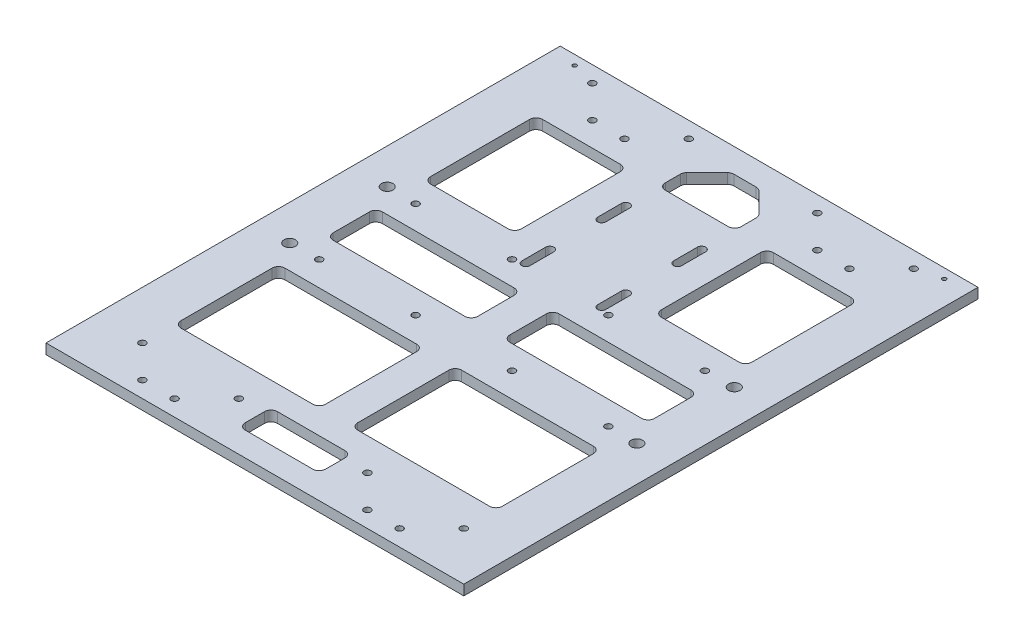
SolidWorks part; units mm, degrees
material "1060 Alloy"
ref_plane "Front Plane" through (0, 0, 0) normal (0, 0, 1) x (1, 0, 0)
ref_plane "Top Plane" through (0, 0, 0) normal (0, 1, 0) x (1, 0, 0)
ref_plane "Right Plane" through (0, 0, 0) normal (1, 0, 0) x (0, 0, -1)
sketch "Sketch1" plane through (0, 0, 0) normal (0, 1, 0) x (1, 0, 0)
  line L1 (-120, 160) -> (120, 160)
  line L2 (-120, 160) -> (-120, -160)
  line L3 (-120, -160) -> (120, -160)
  line L4 (120, 160) -> (120, -160)
  line L5 (-120, 160) -> (120, -160) construction
  line L6 (-120, -160) -> (120, 160) construction
  point P0 (0, 0)
  dimension "D1" = 240
  dimension "D2" = 320
extrude "Boss-Extrude1" add sketch "Sketch1" along normal blind 6.35
hole_wizard "Ø7.1 (7.1) Diameter Hole1" positions "Sketch3" profile "Sketch2" hole size "Ø7.1" standard "ANSI Metric" end condition through all
sketch "Sketch3" plane through (0, 6.35, 0) normal (0, 1, 0) x (1, 0, 0)
  point P0 (-108, 30.32)
  point P2 (108, 30.32)
  point P4 (108, -30.32)
  point P6 (-108, -30.32)
  dimension "D1" = 30.32
  dimension "D2" = 60.64
  dimension "D3" = 108
  dimension "D4" = 108
sketch "Sketch2" plane through (-108, 6.35, -30.32) normal (1, 0, 0) x (0, 0, 1)
  line L0 (0, 0) -> (0, 6.35)
  line L1 (0, 6.35) -> (3.55, 6.35)
  line L2 (3.55, 6.35) -> (3.55, 0)
  line L5 (3.55, 0) -> (0, 0)
  line L11 (0, -6.35) -> (0, 107.95) construction
  dimension "Thru Hole Dia." = 7.1
  dimension "Thru Hole Depth" = 6.35
hole_wizard "M5x0.8 Tapped Hole1" positions "Sketch5" profile "Sketch4" tap size "M5x0.8" standard "ANSI Metric" end condition through all
sketch "Sketch5" plane through (0, 6.35, 0) normal (0, 1, 0) x (1, 0, 0)
  point P0 (-90, 30)
  point P4 (-30, 30)
  point P6 (30, 30)
  point P10 (90, 30)
  point P12 (-90, -30)
  point P16 (-30, -30)
  point P18 (30, -30)
  point P22 (90, -30)
  dimension "D1" = 60
  dimension "D2" = 60
  dimension "D3" = 60
  dimension "D4" = 60
  dimension "D5" = 30
  dimension "D6" = 30
sketch "Sketch4" plane through (-90, 6.35, -30) normal (1, 0, 0) x (0, 0, 1)
  line L0 (0, 0) -> (0, 6.35)
  line L1 (0, 6.35) -> (2.1, 6.35)
  line L2 (2.1, 6.35) -> (2.1, 0)
  line L5 (2.1, 0) -> (0, 0)
  line L11 (0, -6.35) -> (0, 107.95) construction
  dimension "Thru Tap Drill Dia." = 4.2
  dimension "Thru Tap Drill Depth" = 6.35
cosmetic thread "Hole Thread1" parameters "D2"=5
cosmetic thread "Hole Thread2" parameters "D2"=5
cosmetic thread "Hole Thread3" parameters "D2"=5
cosmetic thread "Hole Thread4" parameters "D2"=5
cosmetic thread "Hole Thread5" parameters "D2"=5
cosmetic thread "Hole Thread6" parameters "D2"=5
cosmetic thread "Hole Thread7" parameters "D2"=5
cosmetic thread "Hole Thread8" parameters "D2"=5
hole_wizard "M5x0.8 Tapped Hole3" positions "Sketch9" profile "Sketch8" tap size "M5x0.8" standard "ANSI Metric" end condition through all
sketch "Sketch9" plane through (0, 6.35, 0) normal (0, 1, 0) x (1, 0, 0)
  line L1 (-120, -160) -> (120, -160) construction
  line L2 (120, 160) -> (-120, 160) construction
  point P0 (-80, -150)
  point P2 (-60, -150)
  point P4 (-40, -130)
  point P6 (-100, -130)
  point P16 (-100, 150)
  point P18 (-80, 130)
  point P20 (-60, 130)
  point P22 (-40, 150)
  point P27 (40, 150)
  point P29 (60, 130)
  point P31 (80, 130)
  point P33 (100, 150)
  point P34 (40, -130)
  point P36 (100, -130)
  point P38 (60, -150)
  point P40 (80, -150)
  dimension "D1" = 20
  dimension "D2" = 10
  dimension "D3" = 30
  dimension "D4" = 20
  dimension "D5" = 20
  dimension "D6" = 40
  dimension "D7" = 20
  dimension "D8" = 20
  dimension "D9" = 20
  dimension "D10" = 20
  dimension "D11" = 20
  dimension "D12" = 30
  dimension "D13" = 40
  dimension "D14" = 40
  dimension "D15" = 60
  dimension "D16" = 20
  dimension "D17" = 20
  dimension "D18" = 20
  dimension "D19" = 20
  dimension "D20" = 30
  dimension "D21" = 20
  dimension "D22" = 40
  dimension "D23" = 20
  dimension "D24" = 20
  dimension "D25" = 20
  dimension "D26" = 20
  dimension "D27" = 10
  dimension "D28" = 30
sketch "Sketch8" plane through (-80, 6.35, 150) normal (1, 0, 0) x (0, 0, 1)
  line L0 (0, 0) -> (0, 6.35)
  line L1 (0, 6.35) -> (2.1, 6.35)
  line L2 (2.1, 6.35) -> (2.1, 0)
  line L5 (2.1, 0) -> (0, 0)
  line L11 (0, -6.35) -> (0, 107.95) construction
  dimension "Thru Tap Drill Dia." = 4.2
  dimension "Thru Tap Drill Depth" = 6.35
cosmetic thread "Hole Thread15" parameters "D2"=5
cosmetic thread "Hole Thread16" parameters "D2"=5
cosmetic thread "Hole Thread17" parameters "D2"=5
cosmetic thread "Hole Thread18" parameters "D2"=5
cosmetic thread "Hole Thread19" parameters "D2"=5
cosmetic thread "Hole Thread20" parameters "D2"=5
cosmetic thread "Hole Thread21" parameters "D2"=5
cosmetic thread "Hole Thread22" parameters "D2"=5
cosmetic thread "Hole Thread23" parameters "D2"=5
cosmetic thread "Hole Thread24" parameters "D2"=5
cosmetic thread "Hole Thread25" parameters "D2"=5
cosmetic thread "Hole Thread26" parameters "D2"=5
cosmetic thread "Hole Thread27" parameters "D2"=5
cosmetic thread "Hole Thread28" parameters "D2"=5
cosmetic thread "Hole Thread29" parameters "D2"=5
cosmetic thread "Hole Thread30" parameters "D2"=5
hole_wizard "Ø5.0mm Clearance Dowel Slot1" positions "Sketch11" profile "Sketch10" size "Ø5.0" standard "ANSI Metric" slot yes end condition through all
sketch "Sketch11" plane through (0, 6.35, 0) normal (0, 1, 0) x (1, 0, 0)
  line L5 (-23.6, 76.88) -> (-23.6, 96.88) construction
  line L7 (-23.6, 86.88) -> (23.6, 86.88) construction
  line L10 (0, 86.88) -> (0, 63.28) construction
  circle A0 centre (108, 30.32) radius 3.55 construction
  point P0 (-23.6, 86.88)
  point P2 (23.6, 86.88)
  point P4 (-23.6, 39.68)
  point P6 (23.6, 39.68)
  dimension "D1" = 47.2
  dimension "D2" = 47.2
  dimension "D3" = 47.2
  dimension "D4" = 47.2
  dimension "D5" = 9.36
  dimension "D6" = 23.6
  dimension "D7" = 20
sketch "Sketch10" plane through (-23.6, 6.35, -86.88) normal (1, 0, 0) x (0, 0, 1)
  line L0 (0, 0) -> (0, 6.35)
  line L1 (0, 6.35) -> (2.55, 6.35)
  line L2 (2.55, 6.35) -> (2.55, 0)
  line L5 (2.55, 0) -> (0, 0)
  line L11 (0, -6.35) -> (0, 107.95) construction
  dimension "Thru Hole Dia." = 5.1
  dimension "Thru Hole Depth" = 6.35
sketch "Sketch12" plane through (0, 6.35, 0) normal (0, 1, 0) x (1, 0, 0)
  line L0 (-120, 160) -> (-120, -160) construction
  line L1 (-23.6, 130) -> (-8.6, 145)
  line L2 (-100, 115) -> (-43.6, 115)
  line L3 (-100, 115) -> (-100, 45.32)
  line L4 (-100, 45.32) -> (-43.6, 45.32)
  line L5 (-43.6, 115) -> (-43.6, 45.32)
  line L6 (-8.6, 145) -> (0, 145)
  line L7 (0, 145) -> (0, 130)
  line L8 (0, 130) -> (-23.6, 130)
  line L9 (120, 160) -> (-120, 160) construction
  line L10 (-100, 15.32) -> (-10, 15.32)
  line L11 (-100, 15.32) -> (-100, -15.32)
  line L12 (-100, -15.32) -> (-10, -15.32)
  line L14 (-10, 15.32) -> (-10, -15.32)
  line L15 (0, -125) -> (-25, -125)
  line L16 (0, -125) -> (0, -145)
  line L17 (0, -145) -> (-25, -145)
  line L18 (-25, -125) -> (-25, -145)
  line L19 (-100, -45.32) -> (-10, -45.32)
  line L20 (-100, -45.32) -> (-100, -110)
  line L21 (-100, -110) -> (-10, -110)
  line L22 (-10, -45.32) -> (-10, -110)
  line L23 (-23.6, 130) -> (-23.6, 115)
  line L24 (-23.6, 115) -> (0, 115)
  line L25 (0, 115) -> (0, 130)
  line L26 (-120, -160) -> (120, -160) construction
  circle A10 centre (-108, 30.32) radius 3.55 construction
  circle A11 centre (-108, -30.32) radius 3.55 construction
  circle A12 centre (-80, 130) radius 2.1 construction
  arc A13 (-21.05, 47.13) -> (-26.15, 47.13) centre (-23.6, 47.13) ccw construction
  circle A14 centre (-100, -130) radius 2.1 construction
  circle A15 centre (-40, -130) radius 2.1 construction
  point P27 (0, 160)
  point P32 (-23.6, 49.68)
  dimension "D3" = 15
  dimension "D7" = 15
  dimension "D10" = 20
  dimension "D15" = 20
  dimension "D8" = 15
  dimension "D1" = 10
  dimension "D2" = 20
  dimension "D4" = 15
  dimension "D5" = 15
  dimension "D6" = 15
  dimension "D9" = 20
  dimension "D11" = 45
  dimension "D12" = 20
  dimension "D13" = 15
  dimension "D14" = 10
  dimension "D16" = 15
  dimension "D17" = 20
  dimension "D18" = 15
  dimension "D19" = 15
  dimension "D20" = 15
extrude "Cut-Extrude1" cut sketch "Sketch12" against normal blind 10 contours L15 L18 L17 L16 | L22 L19 L20 L21 | L5 L2 L3 L4 | L24 L25 L8 L23 | L8 L7 L6 L1 | L12 L14 L10 L11 region at (-8.6323, 6.35, -136.3354) region at (-11.8, 6.35, -122.5) region at (-71.8, 6.35, -80.16) region at (-12.5, 6.35, 135) region at (-55, 6.35, 77.66)
fillet "Fillet1" radius 4 17 edges at (-43.6, 3.175, -45.32) (-10, 3.175, 15.32) (-43.6, 3.175, -115) (-100, 3.175, -115) (-100, 3.175, -45.32) (-23.6, 3.175, -115) (-23.6, 3.175, -130) (-8.6, 3.175, -145) (-25, 3.175, 125) (-25, 3.175, 145) (-100, 3.175, 110) (-100, 3.175, 45.32) (-10, 3.175, -15.32) (-10, 3.175, 110) (-100, 3.175, 15.32) (-10, 3.175, 45.32) (-100, 3.175, -15.32)
ref_plane "Plane1" through (0, 0, 0) normal (-1, 0, 0) x (0, 0, 1)
mirror "Mirror1" about plane through (0, 0, 0) normal (-1, 0, 0) of "Fillet1", "Cut-Extrude1"
sketch "Sketch13" plane through (0, 6.35, 0) normal (0, 1, 0) x (1, 0, 0)
  line L0 (120, 160) -> (-120, 160) construction
  line L1 (-120, 160) -> (-130, 160)
  line L2 (-120, 160) -> (-120, -160)
  line L3 (-120, -160) -> (-130, -160)
  line L4 (-130, 160) -> (-130, -160)
  line L5 (120, -160) -> (130, -160)
  line L6 (120, -160) -> (120, 160)
  line L7 (120, 160) -> (130, 160)
  line L8 (130, -160) -> (130, 160)
  line L9 (-120, -160) -> (120, -160) construction
  dimension "D1" = 10
  dimension "D2" = 10
extrude "Boss-Extrude2" add sketch "Sketch13" against normal up to surface (6.35 mm away) up to face at (0, 0, -130.3188)
hole_wizard "M3x0.5 Tapped Hole1" positions "Sketch15" profile "Sketch14" tap size "M3x0.5" standard "ANSI Metric" end condition through all
sketch "Sketch15" plane through (0, 0, 0) normal (0, -1, 0) x (-1, 0, 0)
  line L0 (-130, 160) -> (-130, -160) construction
  line L1 (130, -160) -> (130, 160) construction
  line L2 (-130, 160) -> (130, 160) construction
  point P0 (-115, 154)
  point P2 (115, 154)
  dimension "D1" = 15
  dimension "D2" = 15
  dimension "D3" = 6
  dimension "D4" = 6
sketch "Sketch14" plane through (115, 0, -154) normal (1, 0, 0) x (0, 0, -1)
  line L0 (0, 0) -> (0, 6.35)
  line L1 (0, 6.35) -> (1.25, 6.35)
  line L2 (1.25, 6.35) -> (1.25, 0)
  line L5 (1.25, 0) -> (0, 0)
  line L11 (0, -6.35) -> (0, 107.95) construction
  dimension "Thru Tap Drill Dia." = 2.5
  dimension "Thru Tap Drill Depth" = 6.35
cosmetic thread "Hole Thread33" parameters "D2"=3
cosmetic thread "Hole Thread34" parameters "D2"=3
